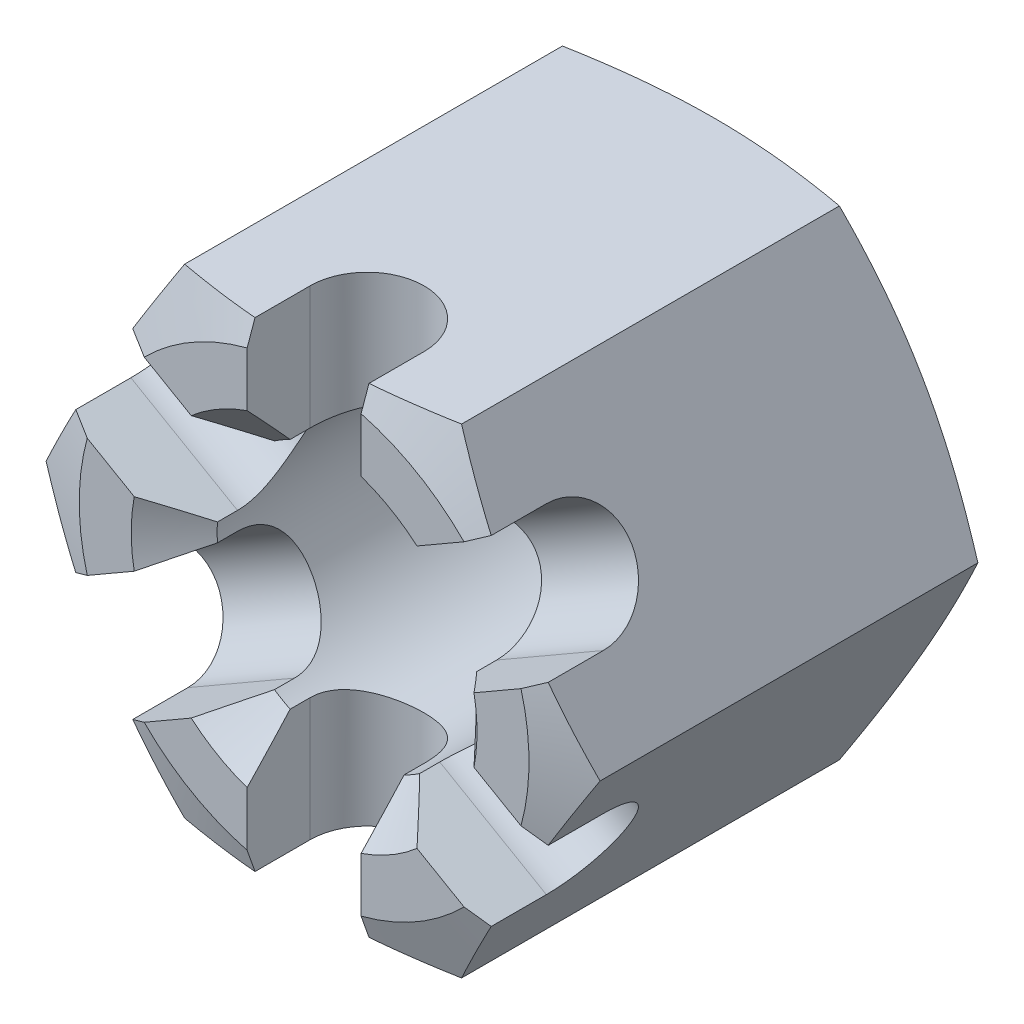
SolidWorks part; units mm, degrees
ref_plane "Front" through (0, 0, 0) normal (0, 0, 1) x (1, 0, 0)
ref_plane "Top" through (0, 0, 0) normal (0, 1, 0) x (1, 0, 0)
ref_plane "Right" through (0, 0, 0) normal (1, 0, 0) x (0, 0, -1)
sketch "Sketch1" plane through (0, 0, 0) normal (0, 0, 1) x (1, 0, 0)
  line L1 (6.9282, -12) -> (13.8564, 0)
  line L2 (13.8564, 0) -> (6.9282, 12)
  line L3 (6.9282, 12) -> (-6.9282, 12)
  line L4 (-6.9282, 12) -> (-13.8564, 0)
  line L5 (-13.8564, 0) -> (-6.9282, -12)
  line L6 (-6.9282, -12) -> (6.9282, -12)
  circle A0 centre (0, 0) radius 12 construction
  dimension "s" = 24
extrude "BaseNut" add sketch "Sketch1" against normal blind 20.8
sketch "Sketch2" plane through (-3.4718, 0, -17.3282) normal (0, 1, 0) x (0, 0, -1)
  line L0 (3.4718, 7.7782) -> (2.5231, 10.3846)
  line L3 (2.5231, 10.3846) -> (3.4718, 10.3846)
  line L4 (3.4718, 10.3846) -> (3.4718, 7.7782)
  line L5 (0, -3.4718) -> (-12.6262, -3.4718) construction
  line L6 (-17.3282, 7.7782) -> (-17.3282, 10.3846)
  line L8 (-17.3282, 10.3846) -> (-16.3795, 10.3846)
  line L9 (-16.3795, 10.3846) -> (-17.3282, 7.7782)
  dimension "dw" = 22.5
  dimension "D2" = 20
  dimension "D3" = 20
revolve "Double-Chamfer" cut sketch "Sketch2" angle 360 about L5
sketch "Sketch3" plane through (-4.2799, -1.7357, -20.8) normal (0, 0, -1) x (-1, 0, 0)
  line L0 (-4.2799, 1.7357) -> (-4.2799, 3.2357) construction
  circle A0 centre (-4.2799, 1.7357) radius 6.5
  circle A1 centre (-4.2799, 1.7357) radius 11.25 construction
  dimension "D1" = 13
  dimension "D2" = 1.5
extrude "Hole" cut sketch "Sketch3" against normal through all
cosmetic thread "ThreadCosmetic1" [suppressed] parameters "D2"=16
sketch "Sketch4" plane through (-15.7583, 0, -7.1083) normal (0, 1, 0) x (0, 0, -1)
  line L0 (13.6917, -24.4083) -> (11.5417, -22.2583)
  line L2 (11.5417, -22.2583) -> (13.6917, -22.2583)
  line L3 (13.6917, -22.2583) -> (13.6917, -24.4083)
  line L4 (0, -15.7583) -> (-22.8666, -15.7583) construction
  line L7 (-7.1083, -22.2583) -> (-4.9583, -22.2583)
  line L9 (-4.9583, -22.2583) -> (-7.1083, -24.4083)
  line L10 (-7.1083, -24.4083) -> (-7.1083, -22.2583)
  dimension "D1" = 17.3
  dimension "D2" = 45
  dimension "D3" = 45
revolve "EndChamfer" cut sketch "Sketch4" angle 360 about L4
sketch "Sketch5" plane through (-17.8, 0, -17.8) normal (0, 1, 0) x (0, 0, -1)
  line L0 (-17.8, -14.95) -> (-14.65, -14.95)
  line L2 (-14.65, -20.65) -> (-17.8, -20.65)
  line L3 (-17.8, -20.65) -> (-17.8, -14.95)
  line L6 (3, -26.45) -> (3, -9.15) construction
  line L8 (-17.8, -9.15) -> (-17.8, -26.45) construction
  arc A0 (-14.65, -14.95) -> (-14.65, -20.65) centre (-14.65, -17.8) cw
  point P2 (-11.8, -17.8)
  point P3 (3, -17.8)
  dimension "W" = 14.8
extrude "Slot" cut sketch "Sketch5" against normal through all
pattern_circular "SlotPattern" count 6 over 360 about axis through (0, 0, -7.1083) along (0, 0, 1) of "Slot"
sketch "Sketch6" plane through (-3.4767, 0, -17.3331) normal (0, 1, 0) x (0, 0, -1)
  line L0 (-17.3331, 0.5233) -> (-11.3331, 0.5233)
  line L1 (-11.3331, 0.5233) -> (-7.7457, 10.3797)
  line L2 (-7.7457, 10.3797) -> (-17.3331, 10.3797)
  line L3 (-17.3331, 10.3797) -> (-17.3331, 0.5233)
  line L7 (0, -3.4767) -> (-20.8098, -3.4767) construction
  line L8 (-17.3331, 7.7733) -> (-17.3331, 7.3733) construction
  line L9 (2.5182, 10.3797) -> (-16.3844, 10.3797) construction
  dimension "D1" = 70
  dimension "D3" = 8
  dimension "D2" = 14.8
revolve "Cut-Revolve1" [suppressed] cut sketch "Sketch6" angle 360 about L7
sketch "Sketch7" plane through (0, 0, 0) normal (0, 1, 0) x (1, 0, 0)
  line L0 (5, 19.4) -> (6.5, 19.4)
  line L1 (6.5, 19.4) -> (7.799, 18.65)
  line L2 (7.799, 18.65) -> (6.5, 17.9)
  line L3 (6.5, 17.9) -> (5, 17.9)
  line L4 (5, 17.9) -> (5, 19.4)
  line L5 (0, 25.358) -> (0, -3.8405) construction
  line L6 (-6.5, 18.65) -> (6.5, 18.65) construction
  dimension "D1" = 1.5
  dimension "D2" = 13
revolve "Cut-Revolve10" [suppressed] cut sketch "Sketch7" angle 360 about L5
pattern_linear "LPattern10" [suppressed] count 10 spacing 1.8 along (0, 0, 1) of bodies 108
equation "\"D2@Sketch6\" = \"W@Sketch5\""
equation "\"D1@Sketch3\" = \"D2@ThreadCosmetic1\" - \"D2@Sketch3\" * 2"
equation "\"D2@Sketch7\" = \"D1@Sketch3\""
equation "\"D1@Sketch7\" = (  \"D2@ThreadCosmetic1\" - \"D1@Sketch3\" )  / 2"
equation "\"D3@LPattern10\" = \"D1@Sketch7\" * 1.2"
equation "\"D1@LPattern10\" = \"m@BaseNut\"  / \"D3@LPattern10\" - 2"
